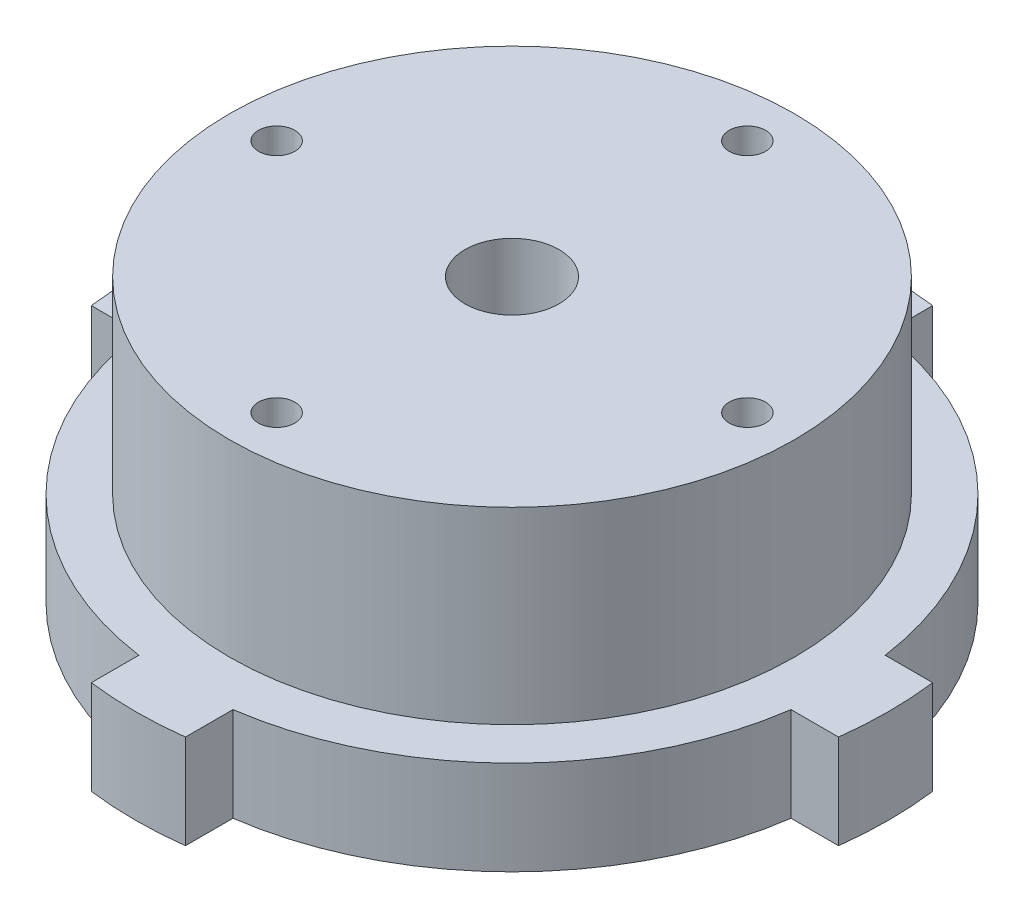
SolidWorks part; units mm, degrees
material "AISI 316 Annealed Stainless Steel Bar (SS)"
ref_plane "Front Plane" through (0, 0, 0) normal (0, 0, 1) x (1, 0, 0)
ref_plane "Top Plane" through (0, 0, 0) normal (0, 1, 0) x (1, 0, 0)
ref_plane "Right Plane" through (0, 0, 0) normal (1, 0, 0) x (0, 0, -1)
sketch "Sketch2" plane through (0, 0, 0) normal (0, 1, 0) x (1, 0, 0)
  line L0 (-6.35, 43.9941) -> (-6.35, 50.4016)
  line L1 (-50.4016, 6.35) -> (-43.9941, 6.35)
  line L2 (-43.9941, -6.35) -> (-50.4016, -6.35)
  line L3 (-6.35, -50.4016) -> (-6.35, -43.9941)
  line L4 (6.35, -43.9941) -> (6.35, -50.4016)
  line L5 (50.4016, -6.35) -> (43.9941, -6.35)
  line L6 (43.9941, 6.35) -> (50.4016, 6.35)
  line L7 (6.35, 50.4016) -> (6.35, 43.9941)
  arc A0 (-6.35, 43.9941) -> (-43.9941, 6.35) centre (0, 0) ccw
  arc A1 (-43.9941, -6.35) -> (-6.35, -43.9941) centre (0, 0) ccw
  arc A2 (6.35, -43.9941) -> (43.9941, -6.35) centre (0, 0) ccw
  arc A3 (6.35, 43.9941) -> (43.9941, 6.35) centre (0, 0) cw
  arc A4 (-6.35, 50.4016) -> (-50.4016, 6.35) centre (0, 0) ccw
  arc A5 (-50.4016, -6.35) -> (-6.35, -50.4016) centre (0, 0) ccw
  arc A6 (6.35, -50.4016) -> (50.4016, -6.35) centre (0, 0) ccw
  arc A7 (50.4016, 6.35) -> (6.35, 50.4016) centre (0, 0) ccw
  circle A8 centre (0, 0) radius 6.35
  circle A9 centre (0, 0) radius 50.8
  circle A11 centre (0, 0) radius 38.1
  dimension "D1" = 50.8
  dimension "D2" = 6.35
  dimension "D4" = 12.7
  dimension "D5" = 0
  dimension "D7" = 6.35
  dimension "D3" = 12.7
extrude "Boss-Extrude2" add sketch "Sketch2" along normal blind 25.4 separate body contours A11 A8 | A9 region at (-37.0224, 0, 0)
extrude "Boss-Extrude3" add sketch "Sketch2<5>" against normal blind 12.7 contours A9 A11 A4 L0 A0 L1 A5 L2 A1 L3 A6 L4 A2 L5 A7 L6 A3 L7 | A9 | A11 A8 region at (-4.9132, 0, -47.1978) region at (-37.0224, 0, 0)
sketch "Sketch2<5>" plane through (0, 0, 0) normal (0, 1, 0) x (1, 0, 0) same geometry as "Sketch2"
hole_wizard "#10 (0.1935) Diameter Hole2" positions "3DSketch1" profile "Sketch5" hole size "#10" standard "ANSI Inch" end condition through all
sketch3d "3DSketch1"
  line L2 (0, -12.7, 6.35) -> (0, -12.7, 31.75) construction
  line L4 (0, -12.7, 6.35) -> (16.355, -12.7, 6.35) construction
  circle A0 centre (0, -12.7, 0) radius 6.35 construction
  point P0 (0, -12.7, 31.75)
  point P11 (0, -6.35, 0)
  dimension "D1" = 25.4
sketch "Sketch5" plane through (0, -12.7, 31.75) normal (1, 0, 0) x (0, 0, -1)
  line L0 (0, 0) -> (0, 38.1)
  line L1 (0, 38.1) -> (2.4574, 38.1)
  line L2 (2.4574, 38.1) -> (2.4574, 0)
  line L5 (2.4574, 0) -> (0, 0)
  line L11 (0, -6.35) -> (0, 107.95) construction
  dimension "Thru Hole Dia." = 4.9149
  dimension "Thru Hole Depth" = 38.1
pattern_circular "CirPattern2" count 4 over 360 about axis through (0, 25.4, 0) along (0, -1, 0) of "#10 (0.1935) Diameter Hole2"
